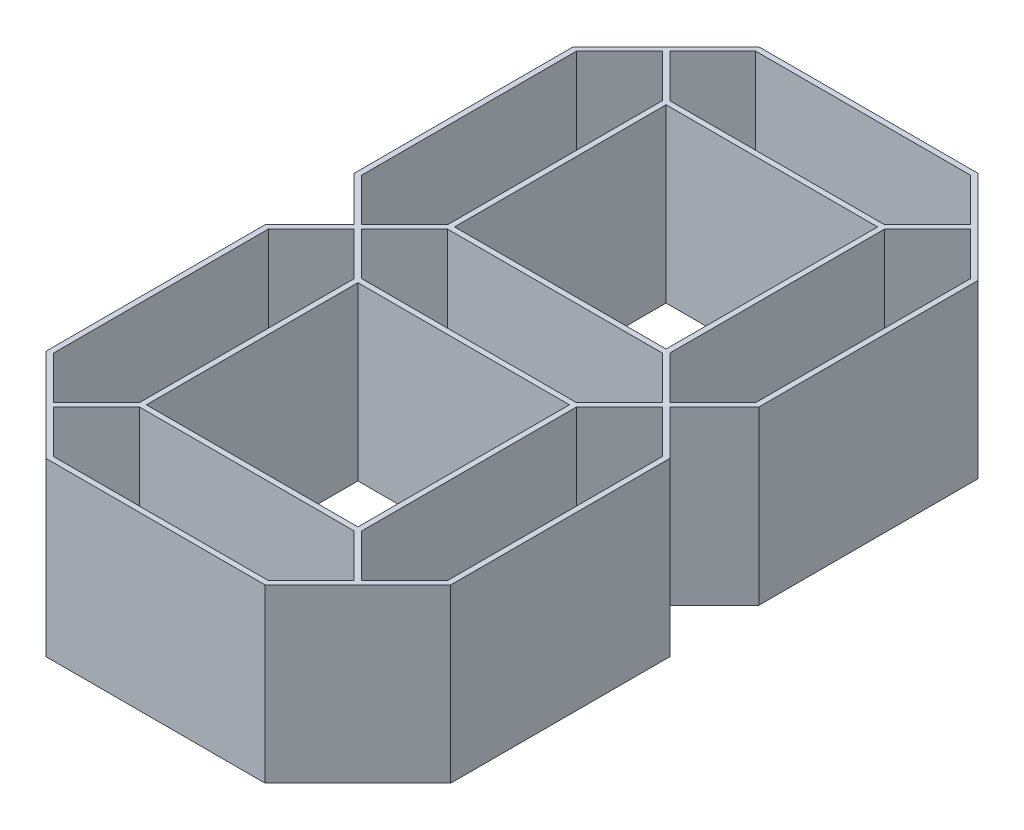
SolidWorks part; units mm, degrees
ref_plane "Front Plane" through (0, 0, 0) normal (0, 0, 1) x (1, 0, 0)
ref_plane "Top Plane" through (0, 0, 0) normal (0, 1, 0) x (1, 0, 0)
ref_plane "Right Plane" through (0, 0, 0) normal (1, 0, 0) x (0, 0, -1)
sketch "Sketch1" plane through (0, 0, 0) normal (0, 1, 0) x (1, 0, 0)
  line L0 (-22.225, 0) -> (-15.875, 6.35)
  line L1 (-15.875, 6.35) -> (15.875, 6.35)
  line L2 (15.875, 6.35) -> (22.225, 0)
  line L3 (22.225, 0) -> (15.875, -6.35)
  line L4 (15.875, -6.35) -> (-15.875, -6.35)
  line L5 (-15.875, -6.35) -> (-22.225, 0)
  line L6 (-9.525, 0) -> (0, 0) construction
  line L7 (0, 0) -> (9.525, 0) construction
  circle A0 centre (-9.525, 0) radius 6
  circle A1 centre (0, 0) radius 6 construction
  circle A2 centre (9.525, 0) radius 6
  point P9 (59.8132, 0)
  point P14 (32.457, 13.0105)
  point P15 (0, 6.35)
  point P16 (35.827, 12.1185)
  dimension "D1" = 12
  dimension "D2" = 19.05
  dimension "D3" = 12.7
  dimension "D4" = 31.75
extrude "Boss-Extrude1" add sketch "Sketch1" along normal blind 1.5875
sketch "Sketch2" plane through (0, 0, 0) normal (0, 1, 0) x (1, 0, 0)
  line L6 (-22.225, 0) -> (-15.875, -6.35)
  line L7 (-15.875, -6.35) -> (15.875, -6.35)
  line L8 (15.875, -6.35) -> (22.225, 0)
  line L9 (22.225, 0) -> (15.875, 6.35)
  line L10 (15.875, 6.35) -> (-15.875, 6.35)
  line L11 (-15.875, 6.35) -> (-22.225, 0)
  line L12 (-22.225, 0) -> (-15.875, -6.35)
  line L13 (-15.875, -6.35) -> (15.875, -6.35)
  line L14 (15.875, -6.35) -> (22.225, 0)
  line L15 (22.225, 0) -> (15.875, 6.35)
  line L16 (15.875, 6.35) -> (-15.875, 6.35)
  line L17 (-15.875, 6.35) -> (-22.225, 0)
  dimension "D1" = 0
extrude "Extrude-Thin1" add sketch "Sketch2" along normal blind 25.4 thin thin type one direction wall 0.7937
sketch "Sketch3" plane through (0, 0, 0) normal (0, 1, 0) x (1, 0, 0)
  line L0 (-19.05, 3.175) -> (-19.6113, 3.7363) construction
  line L1 (-15.875, 6.35) -> (-22.225, 0) construction
  line L2 (-16.2038, 7.1437) -> (-23.3475, 0) construction
  line L3 (-19.3306, 3.4556) -> (0, 22.7863) construction
  line L4 (0, 22.7863) -> (0, 0) construction
  line L5 (0, 0) -> (0, -22.7863) construction
  point P0 (0, 22.7863)
ref_axis "Axis1" through (0, 0, -22.7863) along (0, 1, 0)
ref_axis "Axis2" through (0, 0, 22.7863) along (0, 1, 0)
pattern_circular "CirPattern1" count 4 over 360 about axis through (0, 0, -22.7863) along (0, 1, 0) of "Boss-Extrude1", "Extrude-Thin1"
mirror "Mirror1" about plane through (0, 0, 0) normal (0, 0, 1) of "CirPattern1"
